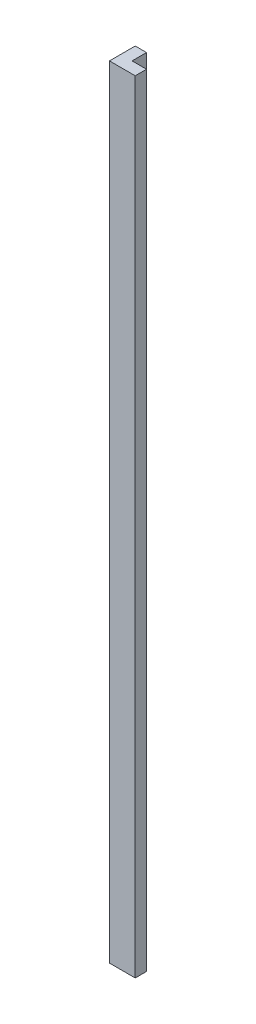
SolidWorks part; units mm, degrees
ref_plane "Front" through (0, 0, 0) normal (0, 0, 1) x (1, 0, 0)
ref_plane "Top" through (0, 0, 0) normal (0, 1, 0) x (1, 0, 0)
ref_plane "Right" through (0, 0, 0) normal (1, 0, 0) x (0, 0, -1)
sketch "Sketch1" plane through (0, 0, 0) normal (0, 1, 0) x (1, 0, 0)
  line L0 (0, 0) -> (0, 231.775)
  line L1 (0, 231.775) -> (101.6, 231.775)
  line L2 (101.6, 231.775) -> (101.6, 101.6)
  line L3 (101.6, 101.6) -> (231.775, 101.6)
  line L4 (231.775, 101.6) -> (231.775, 0)
  line L5 (231.775, 0) -> (0, 0)
  dimension "D1" = 101.6
  dimension "D2" = 231.775
extrude "Boss-Extrude1" add sketch "Sketch1" along normal blind 7023.1
